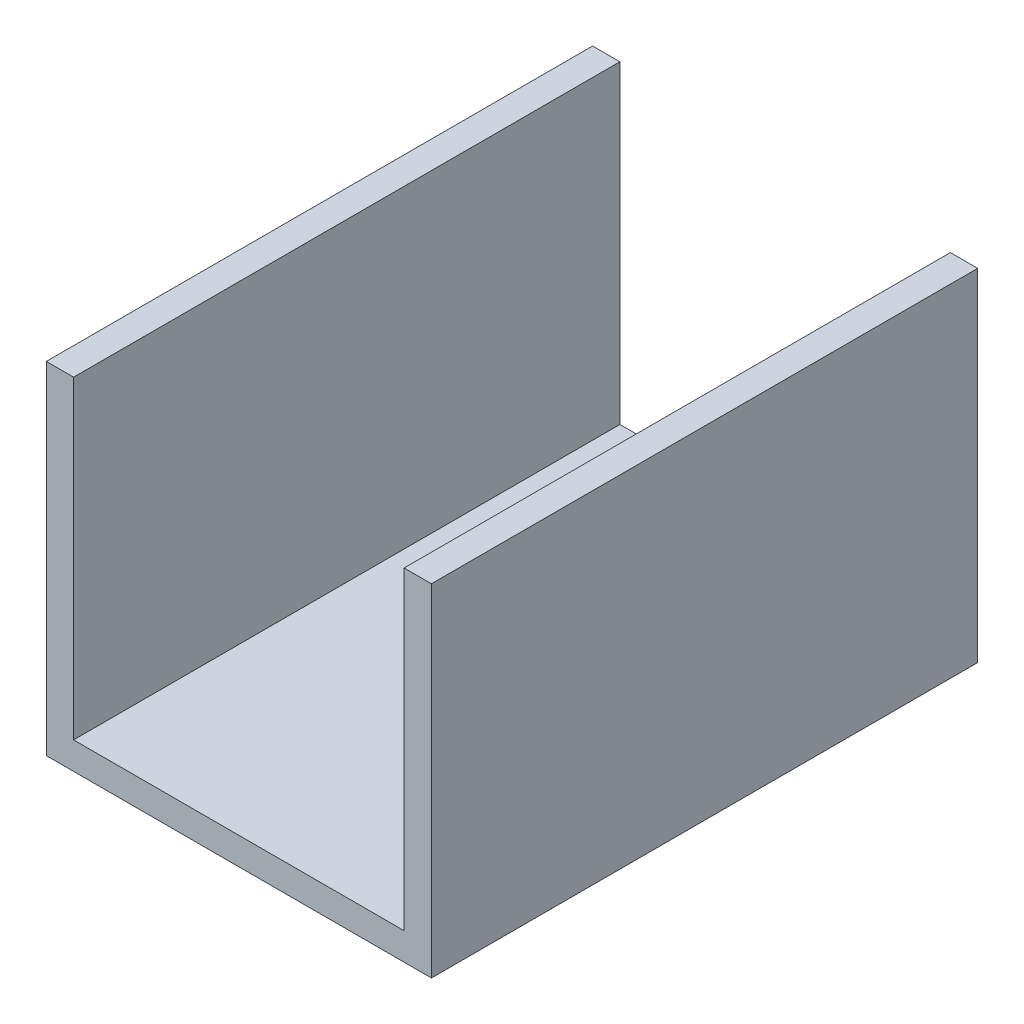
SolidWorks part; units mm, degrees
ref_plane "Front Plane" through (0, 0, 0) normal (0, 0, 1) x (1, 0, 0)
ref_plane "Top Plane" through (0, 0, 0) normal (0, 1, 0) x (1, 0, 0)
ref_plane "Right Plane" through (0, 0, 0) normal (1, 0, 0) x (0, 0, -1)
sketch "Sketch2" plane through (0, 0, 0) normal (0, 0, 1) x (1, 0, 0)
  line L0 (-24.2, 0) -> (24.2, 0)
  line L1 (-24.2, 0) -> (-24.2, 46)
  line L2 (-24.2, 46) -> (-28.2, 46)
  line L3 (-28.2, 46) -> (-28.2, -4)
  line L4 (-28.2, -4) -> (28.2, -4)
  line L5 (28.2, -4) -> (28.2, 46)
  line L6 (28.2, 46) -> (24.2, 46)
  line L7 (24.2, 46) -> (24.2, 0)
  point P4 (0, 0)
  dimension "D1" = 48.4
  dimension "D2" = 4
  dimension "D3" = 4
  dimension "D4" = 50
  dimension "D5" = 56.4
  dimension "D6" = 50
extrude "Boss-Extrude1" add sketch "Sketch2" along normal mid plane 80
